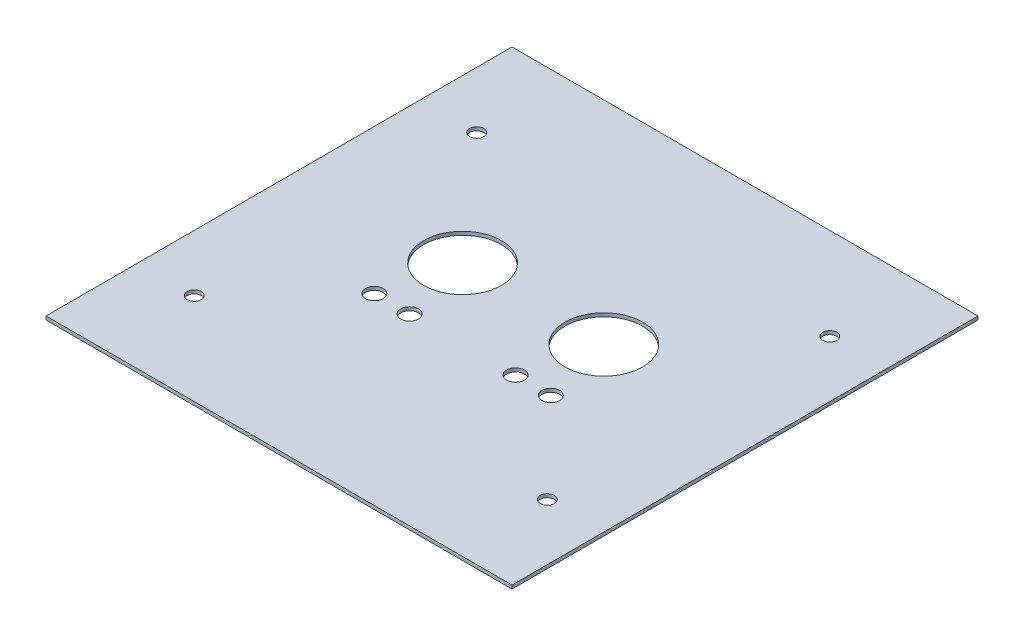
SolidWorks part; units mm, degrees
ref_plane "Front Plane" through (0, 0, 0) normal (0, 0, 1) x (1, 0, 0)
ref_plane "Top Plane" through (0, 0, 0) normal (0, 1, 0) x (1, 0, 0)
ref_plane "Right Plane" through (0, 0, 0) normal (1, 0, 0) x (0, 0, -1)
sketch "Sketch1" plane through (0, 0, 0) normal (0, 1, 0) x (1, 0, 0)
  line L1 (-26.6885, 109.7951) -> (105.3115, 109.7951)
  line L2 (-26.6885, 109.7951) -> (-26.6885, -22.2049)
  line L3 (-26.6885, -22.2049) -> (105.3115, -22.2049)
  line L4 (105.3115, 109.7951) -> (105.3115, -22.2049)
  circle A0 centre (14.3115, 29.7951) radius 2.5
  circle A1 centre (24.3115, 29.7951) radius 2.5
  circle A2 centre (54.3115, 29.7951) radius 2.5
  circle A3 centre (64.3115, 29.7951) radius 2.5
  circle A4 centre (19.3115, 49.7951) radius 11
  circle A5 centre (59.3115, 49.7951) radius 11
  dimension "D3" = 5
  dimension "D6" = 22
  dimension "D1" = 132
  dimension "D2" = 132
  dimension "D4" = 10
  dimension "D5" = 10
  dimension "D7" = 20
  dimension "D8" = 20
  dimension "D9" = 5
  dimension "D10" = 5
  dimension "D11" = 46
  dimension "D12" = 46
  dimension "D13" = 60
  dimension "D14" = 60
extrude "Boss-Extrude1" add sketch "Sketch1" along normal blind 1
sketch "Sketch2" plane through (0, 0, 0) normal (0, -1, 0) x (1, 0, 0)
  circle A0 centre (-10.6885, -3.7951) radius 2
  circle A1 centre (89.3115, -3.7951) radius 2
  circle A2 centre (89.3115, -83.7951) radius 2
  circle A3 centre (-10.6885, -83.7951) radius 2
  dimension "D1" = 4
  dimension "D2" = 4
  dimension "D3" = 4
  dimension "D4" = 4
extrude "Cut-Extrude1" cut sketch "Sketch2" against normal through all
